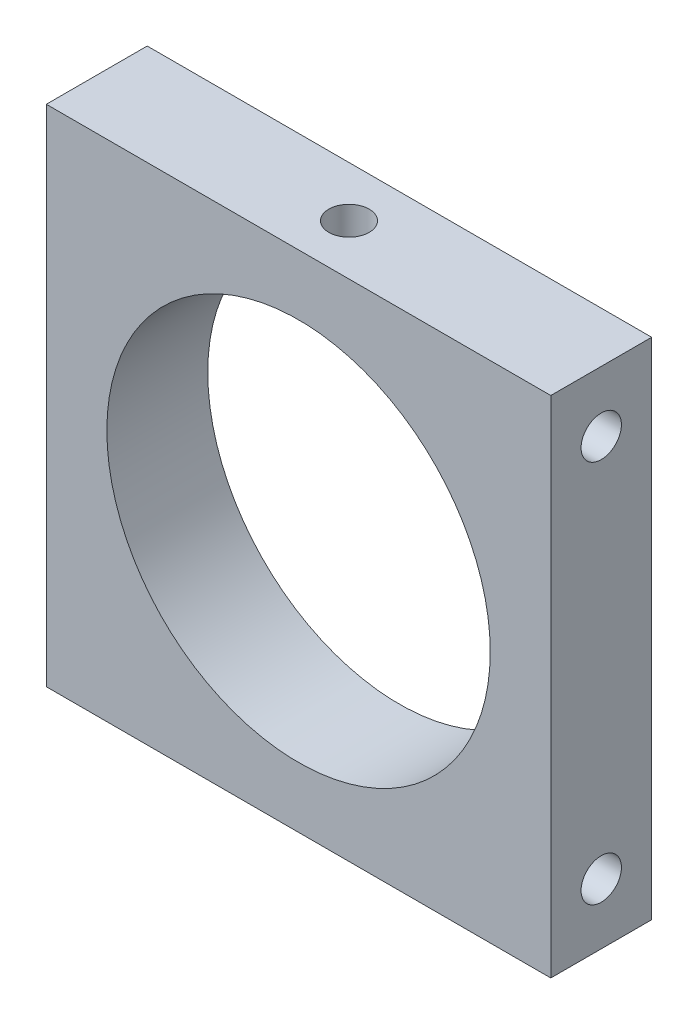
SolidWorks part; units mm, degrees
ref_plane "Plan de face" through (0, 0, 0) normal (0, 0, 1) x (1, 0, 0)
ref_plane "Plan de dessus" through (0, 0, 0) normal (0, 1, 0) x (1, 0, 0)
ref_plane "Plan de droite" through (0, 0, 0) normal (1, 0, 0) x (0, 0, -1)
sketch "Esquisse1" plane through (0, 0, 0) normal (0, 0, 1) x (1, 0, 0)
  line L0 (-38.0783, 2.2337) -> (-25.5783, 2.2337) construction
  line L1 (-38.0783, 14.7337) -> (-13.0783, 14.7337)
  line L2 (-38.0783, 14.7337) -> (-38.0783, -10.2663)
  line L3 (-38.0783, -10.2663) -> (-13.0783, -10.2663)
  line L4 (-13.0783, 14.7337) -> (-13.0783, -10.2663)
  line L5 (-25.5783, 2.2337) -> (-25.5783, 14.7337) construction
  line L6 (-25.5783, -10.2663) -> (-25.5783, 2.2337) construction
  line L7 (-25.5783, 2.2337) -> (-13.0783, 2.2337) construction
  circle A0 centre (-25.5783, 2.2337) radius 9.5
  dimension "D1" = 19
  dimension "D2" = 25
  dimension "D3" = 25
extrude "Boss.-Extru.1" add sketch "Esquisse1" along normal blind 5
sketch "Esquisse2" plane through (-38.0783, 0, 0) normal (-1, 0, 0) x (0, 0, 1)
  line L0 (2.5, 14.7337) -> (2.5, 11.7337) construction
  line L1 (5, 14.7337) -> (0, 14.7337) construction
  line L2 (2.5, 11.7337) -> (2.5, -7.2663) construction
  line L3 (2.5, -7.2663) -> (2.5, -10.2663) construction
  line L4 (5, -10.2663) -> (0, -10.2663) construction
  line L5 (5, 11.7337) -> (2.5, 11.7337) construction
  line L6 (5, 14.7337) -> (5, -10.2663) construction
  line L7 (2.5, 11.7337) -> (0, 11.7337) construction
  line L8 (0, 14.7337) -> (0, -10.2663) construction
  line L9 (5, -7.2663) -> (2.5, -7.2663) construction
  line L10 (2.5, -7.2663) -> (0, -7.2663) construction
  circle A0 centre (2.5, 11.7337) radius 1
  circle A1 centre (2.5, -7.2663) radius 1
  dimension "D1" = 2
  dimension "D2" = 3
extrude "Enlèv. mat.-Extru.1" cut sketch "Esquisse2" against normal blind 2 contours A0 | A1
sketch "Esquisse3" plane through (-13.0783, 0, 0) normal (1, 0, 0) x (0, 0, -1)
  circle A0 centre (-2.5, -7.2663) radius 1
  circle A1 centre (-2.5, 11.7337) radius 1
  circle A2 centre (-2.5, -7.2663) radius 1 construction
  circle A3 centre (-2.5, 11.7337) radius 1 construction
extrude "Enlèv. mat.-Extru.2" cut sketch "Esquisse3" against normal blind 2 contours A1 | A0
sketch "Esquisse4" plane through (0, 14.7337, 0) normal (0, 1, 0) x (1, 0, 0)
  line L0 (-13.0783, -2.5) -> (-25.5783, -2.5) construction
  line L1 (-13.0783, -5) -> (-13.0783, 0) construction
  line L2 (-25.5783, -2.5) -> (-38.0783, -2.5) construction
  line L3 (-38.0783, -5) -> (-38.0783, 0) construction
  circle A0 centre (-25.5783, -2.5) radius 1
  dimension "D1" = 2
extrude "Enlèv. mat.-Extru.3" cut sketch "Esquisse4" against normal up to next contours A0
